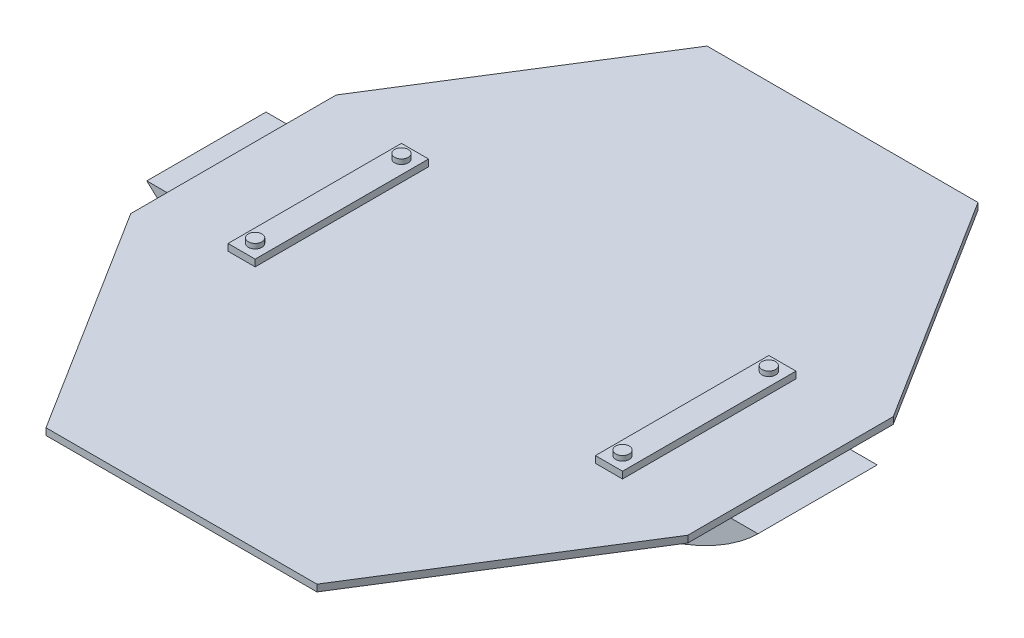
SolidWorks part; units mm, degrees
ref_plane "Front" through (0, 0, 0) normal (0, 0, 1) x (1, 0, 0)
ref_plane "Top" through (0, 0, 0) normal (0, 1, 0) x (1, 0, 0)
ref_plane "Right" through (0, 0, 0) normal (1, 0, 0) x (0, 0, -1)
sketch "Sketch1" plane through (0, 0, 0) normal (0, 0, 1) x (1, 0, 0)
  line L0 (-152.4, 62.23) -> (0, 62.23) construction
  line L1 (-152.4, -62.23) -> (152.4, -62.23) construction
  line L2 (-152.4, -62.23) -> (-152.4, 62.23) construction
  line L3 (-152.4, 62.23) -> (152.4, 62.23) construction
  line L4 (152.4, -62.23) -> (152.4, 62.23) construction
  line L5 (-152.4, -62.23) -> (152.4, 62.23) construction
  line L6 (-152.4, 62.23) -> (152.4, -62.23) construction
  line L7 (-152.4, 62.23) -> (-152.4, -33.02)
  line L8 (-152.4, -33.02) -> (0, -62.23)
  line L9 (0, -62.23) -> (152.4, -32.9764)
  line L10 (152.4, -32.9764) -> (152.4, 62.23)
  line L11 (152.4, 62.23) -> (-152.4, 62.23)
  point P0 (0, 0)
  dimension "D1" = 304.8
  dimension "D2" = 124.46
  dimension "D3" = 95.25
extrude "Boss-Extrude1" add sketch "Sketch1" against normal blind 111.76
ref_plane "Plane1" through (0, 0, -5.08) normal (0, 0, 1) x (1, 0, 0)
sketch "Sketch2" plane through (0, 0, 0) normal (0, 0, 1) x (1, 0, 0)
  line L0 (-152.4, -33.02) -> (-152.4, -13.97) construction
  line L1 (-152.4, 62.23) -> (-152.4, -33.02) construction
  line L2 (152.4, -32.9764) -> (152.4, 62.23) construction
  line L3 (-152.4, -13.97) -> (152.4, -13.97)
  line L4 (-152.4, -13.97) -> (-152.4, 11.43)
  line L5 (-152.4, 11.43) -> (152.4, 11.43)
  line L6 (152.4, -13.97) -> (152.4, 11.43)
  dimension "D1" = 19.05
  dimension "D2" = 25.4
sketch "Sketch5" plane through (0, 0, -5.08) normal (0, 0, 1) x (1, 0, 0)
  line L1 (-152.4, 11.43) -> (152.4, 11.43)
  line L2 (-152.4, 11.43) -> (-152.4, -13.97)
  line L3 (-152.4, -13.97) -> (152.4, -13.97)
  line L4 (152.4, 11.43) -> (152.4, -13.97)
  dimension "D1" = 19.05
  dimension "D2" = 25.4
extrude "Cut-Extrude3" cut sketch "Sketch5" against normal blind 101.6
sketch "Sketch3" plane through (0, 62.23, 0) normal (0, 1, 0) x (1, 0, 0)
  line L0 (152.4, 111.76) -> (-152.4, 111.76) construction
  line L1 (-2.54, 5.08) -> (-99.06, 5.08)
  line L2 (-2.54, 5.08) -> (-2.54, 106.68)
  line L3 (-2.54, 106.68) -> (-99.06, 106.68)
  line L4 (-99.06, 5.08) -> (-99.06, 106.68)
  line L5 (152.4, 0) -> (-152.4, 0) construction
  line L6 (0, 0) -> (0, 111.76) construction
  line L7 (2.54, 106.68) -> (99.06, 106.68)
  line L8 (99.06, 5.08) -> (99.06, 106.68)
  line L9 (2.54, 5.08) -> (99.06, 5.08)
  line L10 (2.54, 5.08) -> (2.54, 106.68)
  line L11 (-152.4, 111.76) -> (-152.4, 0) construction
  line L12 (-104.14, 106.68) -> (-152.4, 106.68)
  line L13 (-104.14, 106.68) -> (-104.14, 5.08)
  line L14 (-104.14, 5.08) -> (-152.4, 5.08)
  line L15 (-152.4, 106.68) -> (-152.4, 5.08)
  line L16 (104.14, 5.08) -> (152.4, 5.08)
  line L17 (152.4, 106.68) -> (152.4, 5.08)
  line L18 (104.14, 106.68) -> (152.4, 106.68)
  line L19 (104.14, 106.68) -> (104.14, 5.08)
  dimension "D1" = 2.54
  dimension "D2" = 96.52
  dimension "D3" = 5.08
  dimension "D4" = 5.08
  dimension "D5" = 5.08
  dimension "D6" = 5.08
  dimension "D7" = 5.08
extrude "Cut-Extrude4" cut sketch "Sketch3" against normal through all both and the other way through all
sketch "Sketch6" plane through (-104.14, 0, 0) normal (-1, 0, 0) x (0, 0, 1)
  line L0 (-5.08, 11.43) -> (-106.68, 11.43) construction
  line L1 (-74.9821, 11.43) -> (-36.8821, 11.43)
  line L2 (-74.9821, 11.43) -> (-74.9821, 62.23)
  line L3 (-74.9821, 62.23) -> (-36.8821, 62.23)
  line L4 (-36.8821, 11.43) -> (-36.8821, 62.23)
  line L5 (-5.08, 62.23) -> (-106.68, 62.23) construction
  dimension "D1" = 38.1
extrude "Cut-Extrude5" cut sketch "Sketch6" against normal up to surface (208.28 mm away) up to face at (104.14, 36.83, -55.88)
ref_plane "Plane2" through (0, 0, -36.8821) normal (0, 0, -1) x (-1, 0, 0)
sketch "Sketch7" plane through (0, 0, -36.8821) normal (0, 0, -1) x (-1, 0, 0)
  line L1 (-40.64, 62.23) -> (40.64, 62.23)
  line L2 (-40.64, 62.23) -> (-40.64, 11.43)
  line L3 (-40.64, 11.43) -> (40.64, 11.43)
  line L4 (40.64, 62.23) -> (40.64, 11.43)
  line L5 (60.96, 62.23) -> (142.24, 62.23)
  line L6 (60.96, 62.23) -> (60.96, 11.43)
  line L7 (60.96, 11.43) -> (142.24, 11.43)
  line L8 (142.24, 62.23) -> (142.24, 11.43)
  line L9 (-142.24, 62.23) -> (-60.96, 62.23)
  line L10 (-142.24, 62.23) -> (-142.24, 11.43)
  line L11 (-142.24, 11.43) -> (-60.96, 11.43)
  line L12 (-60.96, 62.23) -> (-60.96, 11.43)
  dimension "D1" = 38.1
  dimension "D2" = 38.1
  dimension "D3" = 38.1
  dimension "D4" = 38.1
  dimension "D5" = 38.1
  dimension "D6" = 38.1
extrude "Boss-Extrude2" add sketch "Sketch7" against normal blind 5.08
ref_plane "Plane3" through (0, 0, -55.9321) normal (0, 0, -1) x (-1, 0, 0)
mirror "Mirror1" about plane through (0, 0, -55.9321) normal (0, 0, -1) of "Boss-Extrude2"
sketch "Sketch9" plane through (-152.4, 0, 0) normal (-1, 0, 0) x (0, 0, 1)
  line L1 (-111.76, 62.23) -> (-106.68, 62.23)
  line L2 (-111.76, 62.23) -> (-111.76, -33.02)
  line L3 (-111.76, -33.02) -> (-106.68, -33.02)
  line L4 (-106.68, 62.23) -> (-106.68, -33.02)
  line L5 (-5.08, -33.02) -> (0, -33.02)
  line L6 (-5.08, -33.02) -> (-5.08, 62.23)
  line L7 (-5.08, 62.23) -> (0, 62.23)
  line L8 (0, -33.02) -> (0, 62.23)
extrude "Boss-Extrude3" add sketch "Sketch9" along normal blind 10.16
sketch "Sketch10" plane through (152.4, 0, 0) normal (1, 0, 0) x (0, 0, -1)
  line L1 (0, 62.23) -> (5.08, 62.23)
  line L2 (0, 62.23) -> (0, -32.9764)
  line L3 (0, -32.9764) -> (5.08, -32.9764)
  line L4 (5.08, 62.23) -> (5.08, -32.9764)
  line L5 (106.68, -32.9764) -> (111.76, -32.9764)
  line L6 (106.68, -32.9764) -> (106.68, 62.23)
  line L7 (106.68, 62.23) -> (111.76, 62.23)
  line L8 (111.76, -32.9764) -> (111.76, 62.23)
extrude "Boss-Extrude4" add sketch "Sketch10" along normal blind 10.16
sketch "Sketch11" plane through (0, 0, 0) normal (0, 0, 1) x (1, 0, 0)
  line L0 (-162.56, -12.7) -> (-119.6963, -39.2882)
  line L1 (-162.56, -33.02) -> (-162.56, 62.23) construction
  line L2 (-152.4, -33.02) -> (0, -62.23) construction
  line L3 (-119.6963, -39.2882) -> (-152.4, -33.02)
  line L4 (-152.4, -33.02) -> (-162.56, -33.02)
  line L5 (-162.56, -33.02) -> (-162.56, -12.7)
  line L6 (0, -75.9725) -> (0, 75.9725) construction
  line L7 (152.4, -33.02) -> (162.56, -33.02)
  line L8 (119.6963, -39.2882) -> (152.4, -33.02)
  line L9 (162.56, -12.7) -> (119.6963, -39.2882)
  line L10 (162.56, -33.02) -> (162.56, -12.7)
  dimension "D1" = 20.32
extrude "Cut-Extrude7" cut sketch "Sketch11" against normal up to surface (111.76 mm away) up to face at (0, -9.9661, -111.76)
fillet "Fillet1" radius 50.8 9 edges at (-162.56, -12.7, -2.54) (-162.56, -12.7, -109.22) (-119.6963, -39.2882, -109.22) (-119.6963, -39.2882, -2.54) (162.56, -12.7, -109.22) (162.56, -12.7, -2.54) (119.7762, -39.2387, -2.54) (119.7762, -39.2387, -109.22) (0, -62.23, -55.88)
sketch "Sketch12" plane through (0, 0, 0) normal (0, 0, 1) x (1, 0, 0)
  line L0 (-162.56, 62.23) -> (-210.82, 62.23)
  line L1 (-162.56, 62.23) -> (-138.5378, -27.6009)
  line L2 (0, -75.9725) -> (0, 75.9725) construction
  line L3 (162.56, 62.23) -> (210.82, 62.23)
  line L4 (162.56, 62.23) -> (138.5378, -27.6009)
  arc A0 (-138.5378, -27.6009) -> (-210.82, 62.23) centre (-87.1093, 87.7772) cw
  arc A1 (138.5378, -27.6009) -> (210.82, 62.23) centre (87.1093, 87.7772) ccw
  dimension "D1" = 48.26
extrude "Boss-Extrude5" add sketch "Sketch12" against normal up to surface (111.76 mm away) up to face at (0.0134, -14.9837, -111.76)
sketch "Sketch13" plane through (0, 0, 0) normal (1, 0, 0) x (0, 0, -1)
  line L0 (36.8821, 62.23) -> (36.8821, 11.43)
  line L1 (36.8821, 11.43) -> (5.08, 11.43)
  line L2 (5.08, 11.43) -> (5.08, -13.97)
  line L3 (5.08, -13.97) -> (106.68, -13.97)
  line L4 (106.68, -13.97) -> (106.68, 11.43)
  line L5 (106.68, 11.43) -> (74.9821, 11.43)
  line L6 (74.9821, 11.43) -> (74.9821, 62.23)
  line L7 (74.9821, 62.23) -> (36.8821, 62.23)
extrude "Cut-Extrude8" cut sketch "Sketch13" against normal up to surface and the other way up to surface up to face at (-166.2475, -0.5666, -55.88) other way up to face at (166.2475, -0.5666, -55.88)
sketch "Sketch14" plane through (0, 0, -111.76) normal (0, 0, -1) x (-1, 0, 0)
  line L0 (-210.82, 62.23) -> (-319.532, 62.23) construction
  line L1 (-210.82, 62.23) -> (-210.82, 6.858) construction
  line L2 (-210.82, 6.858) -> (-281.686, 6.858) construction
  line L3 (-210.82, 62.23) -> (-210.82, -41.656) construction
  line L4 (-210.82, -41.656) -> (-187.706, -41.656) construction
  line L5 (-210.82, 62.23) -> (-210.82, -56.388) construction
  line L6 (-210.82, -56.388) -> (-102.362, -56.388) construction
  line L7 (-319.532, 62.23) -> (-204.3638, 62.23)
  line L8 (-210.82, 62.23) -> (210.82, 62.23) construction
  line L9 (0.0001, -61.304) -> (0.0001, -56.388)
  line L10 (0, 78.6356) -> (0, -143.442) construction
  line L11 (-0.0001, -61.304) -> (-0.0001, -56.388)
  line L12 (319.532, 62.23) -> (204.3638, 62.23)
  arc A0 (-9.5692, -60.3932) -> (9.5697, -60.3958) centre (0.0071, -10.504) ccw construction
  spline S0 degree 3 poles (0.0001, -61.304) (-63.0357, -58.7298) (-184.1329, -59.3413) (-298.3969, 4.9391) (-319.532, 62.23) knots 0 0 0 0 0.522454 1 1 1 1
  spline S1 degree 3 poles (0.0001, -56.388) (-34.2921, -49.6341) (-117.2936, -40.4496) (-194.6742, 7.6042) (-204.3638, 62.23) knots 0 0 0 0 0.415909 1 1 1 1
  spline S2 degree 3 poles (-0.0001, -61.304) (63.0357, -58.7298) (184.1329, -59.3413) (298.3969, 4.9391) (319.532, 62.23) knots 0 0 0 0 0.522454 1 1 1 1
  spline S3 degree 3 poles (-0.0001, -56.388) (34.2921, -49.6341) (117.2936, -40.4496) (194.6742, 7.6042) (204.3638, 62.23) knots 0 0 0 0 0.415909 1 1 1 1
  dimension "D1" = 108.712
  dimension "D2" = 55.372
  dimension "D3" = 70.866
  dimension "D4" = 103.886
  dimension "D5" = 23.114
  dimension "D6" = 118.618
  dimension "D7" = 108.458
extrude "Boss-Extrude6" add sketch "Sketch14" against normal up to surface (111.76 mm away) contours L11 S3 L12 S2 | S1 L7 S0 L9 up to face at (0.016, -22.2164, 0)
sketch "Sketch15" plane through (0, 0, 0) normal (1, 0, 0) x (0, 0, -1)
  line L0 (36.8821, 62.23) -> (36.8821, 11.43)
  line L1 (36.8821, 11.43) -> (5.08, 11.43)
  line L2 (5.08, 11.43) -> (5.08, -13.97)
  line L3 (5.08, -13.97) -> (106.68, -13.97)
  line L4 (106.68, -13.97) -> (106.68, 11.43)
  line L5 (106.68, 11.43) -> (74.9821, 11.43)
  line L6 (74.9821, 11.43) -> (74.9821, 62.23)
  line L7 (74.9821, 62.23) -> (36.8821, 62.23)
extrude "Cut-Extrude9" cut sketch "Sketch15" along normal blind 241.3 and the other way blind 241.3
sketch "Sketch16" plane through (0, 0, 0) normal (1, 0, 0) x (0, 0, -1)
  line L0 (36.8821, 62.23) -> (74.9821, 62.23)
  line L1 (74.9821, 62.23) -> (74.9821, 11.43)
  line L2 (74.9821, 11.43) -> (36.8821, 11.43)
  line L3 (36.8821, 11.43) -> (36.8821, 62.23)
extrude "Cut-Extrude10" cut sketch "Sketch16" against normal up to surface and the other way up to surface up to face at (-43.3051, -45.7279, -55.88) other way up to face at (43.2842, -45.7287, -55.88)
sketch "Sketch17" plane through (0, 0, 0) normal (1, 0, 0) x (0, 0, -1)
  line L0 (111.76, -61.143) -> (111.76, 62.23) construction
  line L1 (0, 62.23) -> (111.76, 62.23)
  line L2 (0, 62.23) -> (0, 11.43)
  line L3 (0, 11.43) -> (111.76, 11.43)
  line L4 (111.76, 62.23) -> (111.76, 11.43)
  line L5 (0, 62.23) -> (111.76, 11.43) construction
  line L6 (0, 11.43) -> (111.76, 62.23) construction
  point P4 (55.88, 36.83)
extrude "Cut-Extrude11" cut sketch "Sketch17" against normal up to surface and the other way up to surface
sketch "Sketch19" plane through (0, 0, 0) normal (0, 0, 1) x (1, 0, 0)
  line L1 (-286.5096, 11.43) -> (286.5096, 11.43)
  line L2 (-286.5096, 11.43) -> (-286.5096, 17.78)
  line L3 (-286.5096, 17.78) -> (286.5096, 17.78)
  line L4 (286.5096, 11.43) -> (286.5096, 17.78)
  line L5 (-286.5096, 11.43) -> (286.5096, 17.78) construction
  line L6 (-286.5096, 17.78) -> (286.5096, 11.43) construction
  point P4 (0, 14.605)
  dimension "D1" = 6.35
extrude "Boss-Extrude7" add sketch "Sketch19" against normal blind 365.76 and the other way blind 254
sketch "Sketch20" plane through (0, 11.43, 0) normal (0, -1, 0) x (1, 0, 0)
  line L0 (286.5096, 0) -> (126.9976, 254)
  line L1 (-286.5096, 254) -> (286.5096, 254) construction
  line L2 (126.9976, 254) -> (286.5096, 254)
  line L3 (-126.9976, 254) -> (-286.5096, 0)
  line L4 (286.5096, 254) -> (286.5096, 0)
  line L5 (-126.9976, 254) -> (-286.5096, 254)
  line L6 (-286.5096, 254) -> (-286.5096, 0)
  line L7 (286.5096, -55.88) -> (-286.5096, -55.88) construction
  line L8 (286.5096, -111.76) -> (286.5096, 0) construction
  line L9 (-286.5096, 0) -> (-286.5096, -111.76) construction
  line L10 (-126.9976, -365.76) -> (-286.5096, -365.76)
  line L11 (-126.9976, -365.76) -> (-286.5096, -111.76)
  line L12 (-286.5096, -365.76) -> (-286.5096, -111.76)
  line L13 (126.9976, -365.76) -> (286.5096, -365.76)
  line L14 (286.5096, -111.76) -> (126.9976, -365.76)
  line L15 (286.5096, -365.76) -> (286.5096, -111.76)
  dimension "D1" = 159.512
  dimension "D2" = 159.512
extrude "Cut-Extrude12" cut sketch "Sketch20" against normal up to surface (6.35 mm away) contours L13 L15 L14 | L4 L0 L2 | L6 L3 L5 | L10 L12 L11 up to face at (0, 17.78, -55.88)
sketch "Sketch21" plane through (0, 0, 0) normal (0, 0, 1) x (1, 0, 0)
  line L0 (-286.5096, 17.78) -> (-126.9976, 17.78) construction
  line L1 (-286.5096, 11.43) -> (-261.1169, 11.43)
  line L2 (-286.5096, 11.43) -> (-286.5096, 17.78)
  line L3 (-286.5096, 17.78) -> (-261.1169, 17.78)
  line L4 (-261.1169, 11.43) -> (-261.1169, 17.78)
  line L5 (-286.5096, 11.43) -> (-261.1169, 17.78) construction
  line L6 (-286.5096, 17.78) -> (-261.1169, 11.43) construction
  line L7 (0, 17.78) -> (0, -93.4296) construction
  line L8 (126.9976, 17.78) -> (-126.9976, 17.78) construction
  line L9 (286.5096, 11.43) -> (286.5096, 17.78)
  line L10 (286.5096, 11.43) -> (261.1169, 11.43)
  line L11 (261.1169, 11.43) -> (261.1169, 17.78)
  line L12 (286.5096, 17.78) -> (261.1169, 17.78)
  point P4 (-273.8133, 14.605)
extrude "Cut-Extrude13" cut sketch "Sketch21" against normal up to next and the other way up to next
sketch "Sketch22" plane through (0, 0, 0) normal (0, 0, 1) x (1, 0, 0)
  line L0 (0, 0) -> (0, -105.5771) construction
  line L1 (-184.9096, -28.4734) -> (-159.5096, -28.4734)
  line L2 (-184.9096, -28.4734) -> (-184.9096, -34.8234)
  line L3 (-184.9096, -34.8234) -> (-159.5096, -34.8234)
  line L4 (-159.5096, -28.4734) -> (-159.5096, -34.8234)
  line L5 (-184.9096, -28.4734) -> (-159.5096, -34.8234) construction
  line L6 (-184.9096, -34.8234) -> (-159.5096, -28.4734) construction
  line L7 (184.9096, -34.8234) -> (159.5096, -34.8234)
  line L8 (159.5096, -28.4734) -> (159.5096, -34.8234)
  line L9 (184.9096, -28.4734) -> (159.5096, -28.4734)
  line L10 (184.9096, -28.4734) -> (184.9096, -34.8234)
  point P4 (-172.2096, -31.6484)
  dimension "D1" = 114.3
  dimension "D2" = 6.35
  dimension "D3" = 25.4
extrude "Boss-Extrude8" add sketch "Sketch22" along normal blind 25.4
ref_plane "Plane4" through (0, 0, -55.88) normal (0, 0, -1) x (-1, 0, 0)
mirror "Mirror2" about plane through (0, 0, -55.88) normal (0, 0, -1) of "Boss-Extrude8"
sketch "Sketch23" plane through (0, 11.43, 0) normal (0, -1, 0) x (1, 0, 0)
  line L5 (184.9096, -137.16) -> (159.5096, -137.16)
  line L6 (184.9096, -137.16) -> (184.9096, 25.4)
  line L11 (184.9096, 25.4) -> (159.5096, 25.4)
  line L12 (159.5096, -137.16) -> (159.5096, 25.4)
  line L17 (184.9096, -137.16) -> (159.5096, 25.4) construction
  line L18 (184.9096, 25.4) -> (159.5096, -137.16) construction
  line L23 (-159.5096, -137.16) -> (-184.9096, -137.16)
  line L24 (-159.5096, -137.16) -> (-159.5096, 25.4)
  line L25 (-159.5096, 25.4) -> (-184.9096, 25.4)
  line L26 (-184.9096, -137.16) -> (-184.9096, 25.4)
  line L27 (-159.5096, -137.16) -> (-184.9096, 25.4) construction
  line L28 (-159.5096, 25.4) -> (-184.9096, -137.16) construction
  point P4 (172.2096, -55.88)
  point P11 (-172.2096, -55.88)
extrude "Boss-Extrude9" add sketch "Sketch23" against normal blind 12.7
sketch "Sketch24" plane through (0, -34.8234, 0) normal (0, -1, 0) x (1, 0, 0)
  line L0 (184.9096, -137.16) -> (184.9096, -111.76) construction
  line L1 (159.5096, -137.16) -> (184.9096, -137.16) construction
  line L2 (-0.0139, -111.76) -> (-0.0139, 26.5203) construction
  line L3 (-4.0615, -111.76) -> (4.0336, -111.76) construction
  line L4 (286.5096, -55.88) -> (-336.2581, -55.88) construction
  line L5 (286.5096, -111.76) -> (286.5096, 0) construction
  line L6 (-40.0039, -55.88) -> (40.0039, -55.88) construction
  circle A0 centre (172.2096, -124.46) radius 6.3931
  circle A1 centre (172.2096, 12.7) radius 6.3931
  circle A2 centre (-172.2375, 12.7) radius 6.3931
  circle A3 centre (-172.2375, -124.46) radius 6.3931
  dimension "D1" = 12.7
  dimension "D2" = 12.7
extrude "Boss-Extrude10" add sketch "Sketch24" along normal blind 5.08 and the other way blind 63.5
